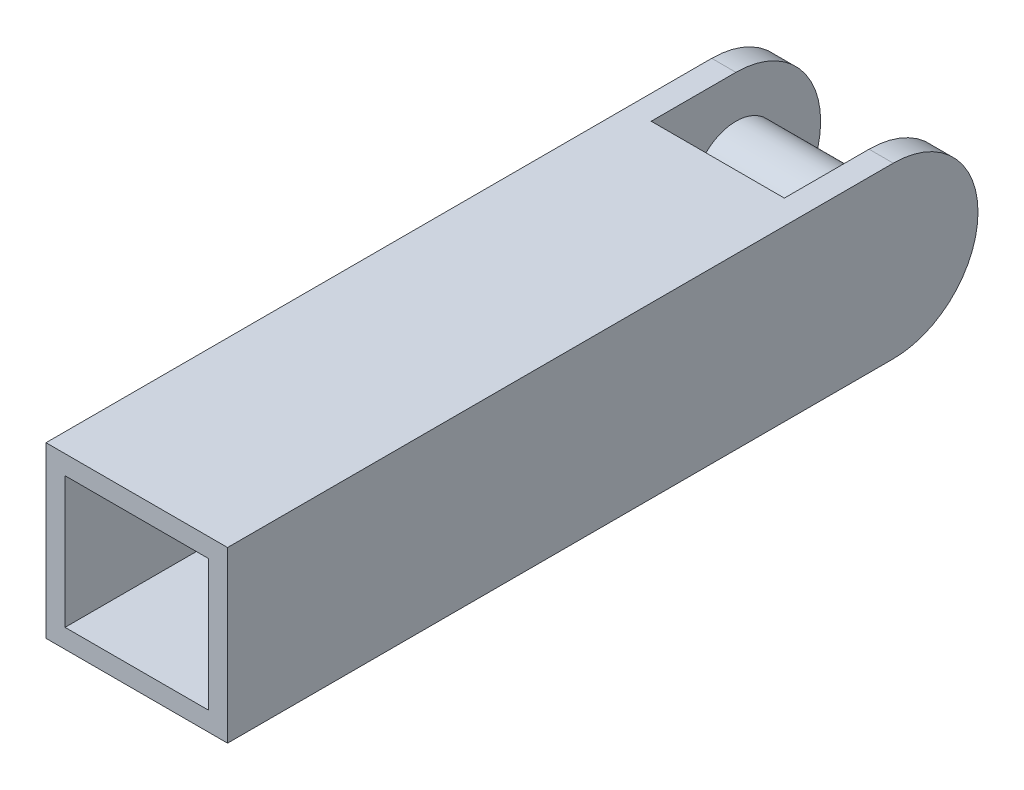
SolidWorks part; units mm, degrees
ref_plane "Front Plane" through (0, 0, 0) normal (0, 0, 1) x (1, 0, 0)
ref_plane "Top Plane" through (0, 0, 0) normal (0, 1, 0) x (1, 0, 0)
ref_plane "Right Plane" through (0, 0, 0) normal (1, 0, 0) x (0, 0, -1)
sketch "Sketch1" plane through (0, 0, 0) normal (1, 0, 0) x (0, 0, -1)
  circle A0 centre (0, 0) radius 22.225
  dimension "D1" = 44.45
extrude "Boss-Extrude1" add sketch "Sketch1" along normal mid plane 69.85
sketch "Sketch2" plane through (0, 0, 0) normal (1, 0, 0) x (0, 0, -1)
  line L0 (-44.45, 44.45) -> (-44.45, -44.45)
  line L1 (0, -44.45) -> (-349.25, -44.45)
  line L2 (0, 44.45) -> (-349.25, 44.45)
  line L3 (-349.25, -44.45) -> (-349.25, 44.45)
  arc A0 (0, -44.45) -> (0, 44.45) centre (0, 0) ccw
  circle A1 centre (0, 0) radius 44.45 construction
  dimension "D1" = 44.45
  dimension "D2" = 304.8
extrude "Boss-Extrude2" add sketch "Sketch2" against normal blind 12.7 from surface contours L1 A0 L2 L0 region at (0, 0, 4.1494) starting at face at (-34.925, 0, -22.225)
extrude "Boss-Extrude3" add sketch "Sketch2<3>" against normal up to surface (47.625 mm away) contours L3 L1 L0 L2 region at (0, 0, 196.85) up to face at (-47.625, 0, 11.1125)
sketch "Sketch2<3>" plane through (0, 0, 0) normal (1, 0, 0) x (0, 0, -1) same geometry as "Sketch2"
mirror "Mirror6" about plane through (0, 0, 0) normal (1, 0, 0) of bodies 103
sketch "Sketch3" plane through (0, 0, 349.25) normal (0, 0, 1) x (1, 0, 0)
  line L8 (37.625, 34.45) -> (-37.625, 34.45)
  line L9 (-37.625, 34.45) -> (-37.625, -34.45)
  line L10 (-37.625, -34.45) -> (37.625, -34.45)
  line L11 (37.625, -34.45) -> (37.625, 34.45)
  line L12 (37.625, 34.45) -> (-37.625, 34.45)
  line L13 (-37.625, 34.45) -> (-37.625, -34.45)
  line L14 (-37.625, -34.45) -> (37.625, -34.45)
  line L15 (37.625, -34.45) -> (37.625, 34.45)
  dimension "D1" = 10
extrude "Cut-Extrude1" cut sketch "Sketch3" against normal blind 149.86
